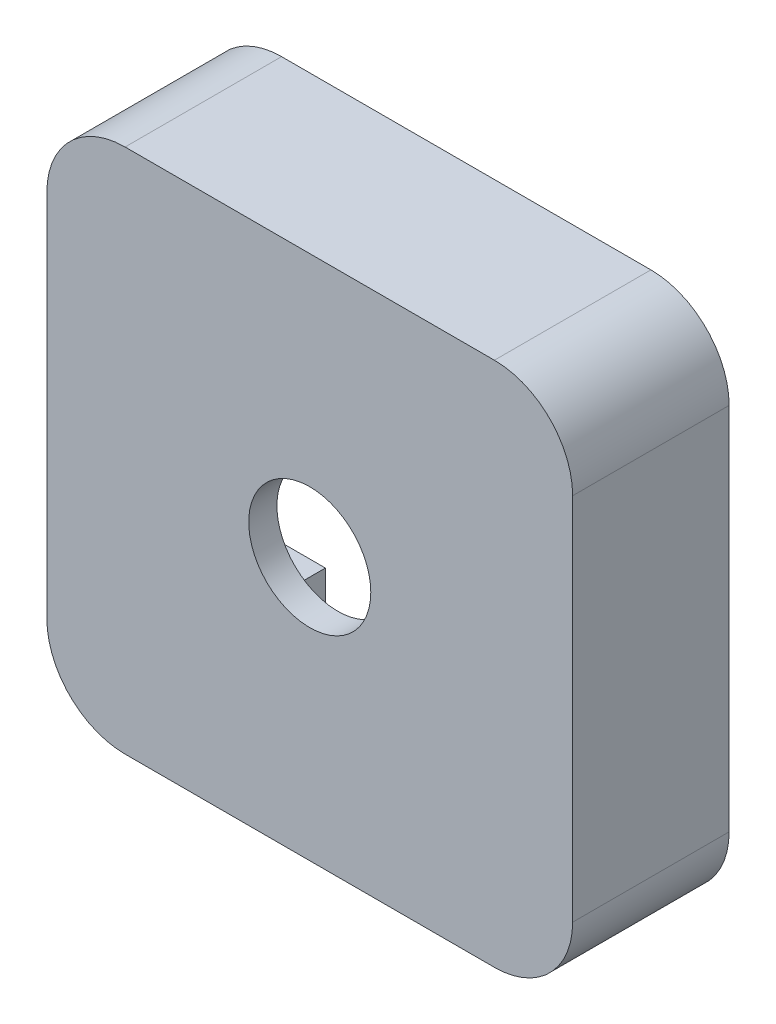
SolidWorks part; units mm, degrees
ref_plane "Front Plane" through (0, 0, 0) normal (0, 0, 1) x (1, 0, 0)
ref_plane "Top Plane" through (0, 0, 0) normal (0, 1, 0) x (1, 0, 0)
ref_plane "Right Plane" through (0, 0, 0) normal (1, 0, 0) x (0, 0, -1)
sketch "Sketch1" plane through (0, 0, 0) normal (0, 0, 1) x (1, 0, 0)
  line L1 (-13.3211, 12.4462) -> (11.8789, 12.4462)
  line L2 (-13.3211, 12.4462) -> (-13.3211, -12.4538)
  line L3 (-13.3211, -12.4538) -> (11.8789, -12.4538)
  line L4 (11.8789, 12.4462) -> (11.8789, -12.4538)
  line L5 (-17.5211, 14.4462) -> (16.0789, 14.4462)
  line L6 (-17.5211, 14.4462) -> (-17.5211, -19.1538)
  line L7 (-17.5211, -19.1538) -> (16.0789, -19.1538)
  line L8 (16.0789, 14.4462) -> (16.0789, -19.1538)
  circle A0 centre (-0.7211, -2.3538) radius 3.9
  dimension "D1" = 7.8
  dimension "D2" = 25.2
  dimension "D3" = 12.6
  dimension "D4" = 14.8
  dimension "D5" = 10.1
  dimension "D6" = 33.6
  dimension "D7" = 16.8
  dimension "D8" = 33.6
  dimension "D9" = 16.8
  dimension "D10" = 2
  dimension "D11" = 6.7
  dimension "D12" = 4.2
  dimension "D13" = 4.2
extrude "Boss-Extrude5" add sketch "Sketch1" against normal blind 1.8 contours L4 L1 L2 L3 A0 region at (-0.7211, 12.092, 0)
extrude "Boss-Extrude6" add sketch "Sketch1<3>" against normal blind 10 contours L8 L5 L6 L7 L1 L4 L3 L2 region at (-0.7211, 13.9711, 0)
sketch "Sketch1<3>" plane through (0, 0, 0) normal (0, 0, 1) x (1, 0, 0) same geometry as "Sketch1"
fillet "Fillet1" radius 5 4 edges at (-17.5211, -19.1538, -5) (16.0789, -19.1538, -5) (16.0789, 14.4462, -5) (-17.5211, 14.4462, -5)
sketch "Sketch3" plane through (0, 0, -10) normal (0, 0, -1) x (-1, 0, 0)
  line L0 (13.3211, -12.4538) -> (-11.8789, -12.4538) construction
  line L1 (-8.2789, -12.4538) -> (9.7211, -12.4538)
  line L2 (-8.2789, -12.4538) -> (-8.2789, -19.1538)
  line L3 (-8.2789, -19.1538) -> (9.7211, -19.1538)
  line L4 (9.7211, -12.4538) -> (9.7211, -19.1538)
  line L5 (12.5211, -19.1538) -> (-11.0789, -19.1538) construction
  line L7 (9.7211, -12.4538) -> (17.5211, -12.4538)
  line L8 (17.5211, 9.4462) -> (17.5211, -14.1538) construction
  line L9 (-8.2789, -12.4538) -> (-16.0789, -12.4538)
  line L10 (-16.0789, 9.4462) -> (-16.0789, -14.1538) construction
  line M5 (-11.0789, -19.1538) -> (12.5211, -19.1538)
  line M15 (13.3211, -12.4538) -> (-11.8789, -12.4538)
  dimension "D1" = 18
extrude "Cut-Extrude1" cut sketch "Sketch3" against normal blind 3.8 contours L4 L2 M15 M5 region at (-0.7211, -15.8038, -10)
equation "\"D2@Sketch1\"=25.2mm"
equation "\"D3@Sketch1\"=\"D2@Sketch1\"/2"
equation "\"D6@Sketch1\"=\"D2@Sketch1\"+8.4"
equation "\"D7@Sketch1\"=\"D6@Sketch1\"/2"
equation "\"D8@Sketch1\"=\"D6@Sketch1\""
equation "\"D9@Sketch1\"=\"D8@Sketch1\"/2"
equation "\"D1@Cut-Extrude1\"=10.00-6.2mm"
